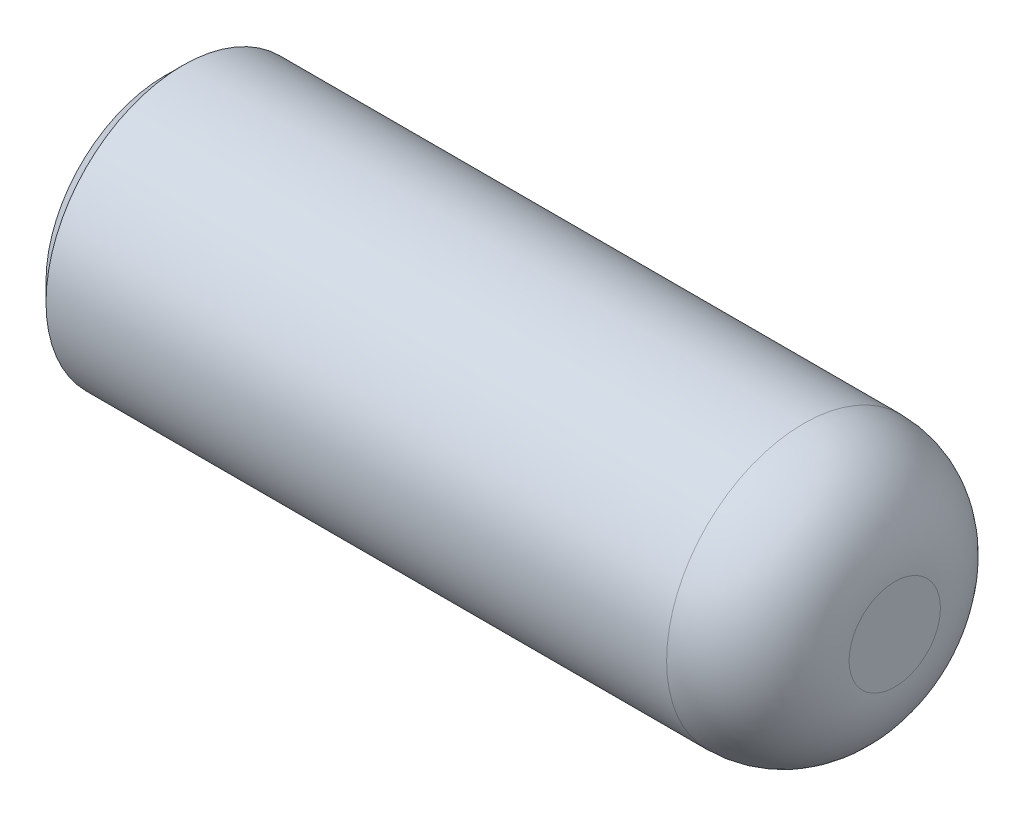
SolidWorks part; units mm, degrees
ref_plane "Front Plane" through (0, 0, 0) normal (0, 0, 1) x (1, 0, 0)
ref_plane "Top Plane" through (0, 0, 0) normal (0, 1, 0) x (1, 0, 0)
ref_plane "Right Plane" through (0, 0, 0) normal (1, 0, 0) x (0, 0, -1)
sketch "Sketch1" plane through (0, 0, 0) normal (1, 0, 0) x (0, -1, 0)
  circle A0 centre (0, 0) radius 1.5
  dimension "D1" = 3
extrude "Boss-Extrude1" add sketch "Sketch1" along normal mid plane 8
fillet "Fillet1" radius 1 1 edges at (4, 0, -1.5)
chamfer "Chamfer1" distance 0.2 angle 45 1 edges at (-4, 0, -1.5)
